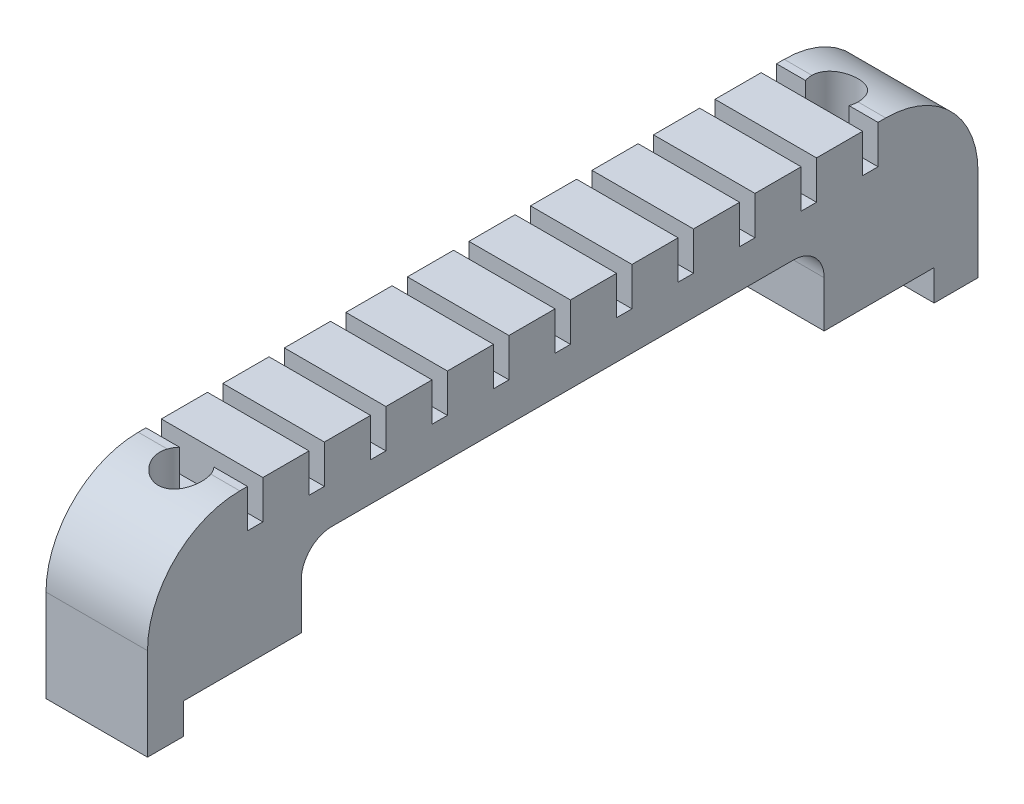
SolidWorks part; units mm, degrees
ref_plane "前视基准面" through (0, 0, 0) normal (0, 0, 1) x (1, 0, 0)
ref_plane "上视基准面" through (0, 0, 0) normal (0, 1, 0) x (1, 0, 0)
ref_plane "右视基准面" through (0, 0, 0) normal (1, 0, 0) x (0, 0, -1)
other "Configuration Table"
sketch "草图1" plane through (0, 0, 0) normal (0, 1, 0) x (1, 0, 0)
  line L0 (-40, 24) -> (40, 24) construction
  line L1 (-40, 24) -> (-40, -24) construction
  line L2 (-40, -24) -> (40, -24) construction
  line L3 (40, 24) -> (40, -24) construction
  line L4 (-40, 24) -> (40, -24) construction
  line L5 (-40, -24) -> (40, 24) construction
  line L6 (-34, 18) -> (34, 18) construction
  line L7 (-34, 18) -> (-34, -18) construction
  line L8 (-34, -18) -> (34, -18) construction
  line L9 (34, 18) -> (34, -18) construction
  line L10 (-34, 18) -> (34, -18) construction
  line L11 (-34, -18) -> (34, 18) construction
  line L13 (-28.3, 27) -> (-21.7, 27)
  line L14 (-28.3, 27) -> (-28.3, -27)
  line L15 (-28.3, -27) -> (-21.7, -27)
  line L16 (-21.7, 27) -> (-21.7, -27)
  line L17 (-28.3, 27) -> (-21.7, -27) construction
  line L18 (-28.3, -27) -> (-21.7, 27) construction
  circle A0 centre (25, -21.5) radius 1.5 construction
  circle A1 centre (25, 21) radius 1.5 construction
  circle A2 centre (0, 21) radius 1.5 construction
  circle A3 centre (0, -21.5) radius 1.5 construction
  circle A4 centre (-25, -21.5) radius 1.5
  circle A5 centre (-25, 21) radius 1.5
  point P0 (0, 0)
  point P17 (0, 0)
  point P22 (-25, 0)
  dimension "D1" = 48
  dimension "D2" = 36
  dimension "D3" = 68
  dimension "D4" = 6.6
  dimension "D5" = 25
  dimension "D6" = 54
extrude "凸台-拉伸1" add sketch "草图1" along normal blind 12
fillet "圆角1" radius 6 2 edges at (-25, 12, -27) (-25, 12, 27)
sketch "草图2" plane through (-28.3, 0, 0) normal (-1, 0, 0) x (0, 0, 1)
  line L1 (-17, 7) -> (17, 7)
  line L2 (-17, 7) -> (-17, -7)
  line L3 (-17, -7) -> (17, -7)
  line L4 (17, 7) -> (17, -7)
  line L5 (-17, 7) -> (17, -7) construction
  line L6 (-17, -7) -> (17, 7) construction
  point P0 (0, 0)
  dimension "D1" = 14
  dimension "D2" = 34
extrude "切除-拉伸1" cut sketch "草图2" against normal blind 20
fillet "圆角2" radius 2 2 edges at (-25, 7, 17) (-25, 7, -17)
sketch "草图3" plane through (-28.3, 0, 0) normal (-1, 0, 0) x (0, 0, 1)
  line L0 (-21, 12) -> (21, 12) construction
  line L1 (-0.5, 9.5) -> (0.5, 9.5)
  line L2 (-0.5, 9.5) -> (-0.5, 12)
  line L3 (-0.5, 12) -> (0.5, 12)
  line L4 (0.5, 9.5) -> (0.5, 12)
  line L5 (-0.5, 9.5) -> (0.5, 12) construction
  line L6 (-0.5, 12) -> (0.5, 9.5) construction
  line L7 (3.5, 9.5) -> (3.5, 12)
  line L8 (3.5, 12) -> (4.5, 12)
  line L9 (4.5, 9.5) -> (4.5, 12)
  line L10 (3.5, 9.5) -> (4.5, 9.5)
  line L11 (7.5, 9.5) -> (7.5, 12)
  line L12 (7.5, 12) -> (8.5, 12)
  line L13 (8.5, 9.5) -> (8.5, 12)
  line L14 (7.5, 9.5) -> (8.5, 9.5)
  line L15 (11.5, 9.5) -> (11.5, 12)
  line L16 (11.5, 12) -> (12.5, 12)
  line L17 (12.5, 9.5) -> (12.5, 12)
  line L18 (11.5, 9.5) -> (12.5, 9.5)
  line L19 (15.5, 9.5) -> (15.5, 12)
  line L20 (15.5, 12) -> (16.5, 12)
  line L21 (16.5, 9.5) -> (16.5, 12)
  line L22 (15.5, 9.5) -> (16.5, 9.5)
  line L23 (19.5, 9.5) -> (19.5, 12)
  line L24 (19.5, 12) -> (20.5, 12)
  line L25 (20.5, 9.5) -> (20.5, 12)
  line L26 (19.5, 9.5) -> (20.5, 9.5)
  line L27 (-4.5, 9.5) -> (-3.5, 9.5)
  line L28 (-4.5, 9.5) -> (-4.5, 12)
  line L29 (-4.5, 12) -> (-3.5, 12)
  line L30 (-3.5, 9.5) -> (-3.5, 12)
  line L31 (-4.5, 9.5) -> (-3.5, 12) construction
  line L32 (-4.5, 12) -> (-3.5, 9.5) construction
  line L33 (-8.5, 9.5) -> (-7.5, 9.5)
  line L34 (-8.5, 9.5) -> (-8.5, 12)
  line L35 (-8.5, 12) -> (-7.5, 12)
  line L36 (-7.5, 9.5) -> (-7.5, 12)
  line L37 (-8.5, 9.5) -> (-7.5, 12) construction
  line L38 (-8.5, 12) -> (-7.5, 9.5) construction
  line L39 (-12.5, 9.5) -> (-11.5, 9.5)
  line L40 (-12.5, 9.5) -> (-12.5, 12)
  line L41 (-12.5, 12) -> (-11.5, 12)
  line L42 (-11.5, 9.5) -> (-11.5, 12)
  line L43 (-12.5, 9.5) -> (-11.5, 12) construction
  line L44 (-12.5, 12) -> (-11.5, 9.5) construction
  line L45 (-16.5, 9.5) -> (-15.5, 9.5)
  line L46 (-16.5, 9.5) -> (-16.5, 12)
  line L47 (-16.5, 12) -> (-15.5, 12)
  line L48 (-15.5, 9.5) -> (-15.5, 12)
  line L49 (-16.5, 9.5) -> (-15.5, 12) construction
  line L50 (-16.5, 12) -> (-15.5, 9.5) construction
  line L51 (-20.5, 9.5) -> (-19.5, 9.5)
  line L52 (-20.5, 9.5) -> (-20.5, 12)
  line L53 (-20.5, 12) -> (-19.5, 12)
  line L54 (-19.5, 9.5) -> (-19.5, 12)
  line L55 (-20.5, 9.5) -> (-19.5, 12) construction
  line L56 (-20.5, 12) -> (-19.5, 9.5) construction
  point P0 (0, 10.75)
  point P30 (-4, 10.75)
  point P35 (-8, 10.75)
  point P40 (-12, 10.75)
  point P45 (-16, 10.75)
  point P50 (-20, 10.75)
  dimension "D1" = 1
  dimension "D2" = 2.5
extrude "切除-拉伸2" cut sketch "草图3" against normal through all
sketch "草图4" plane through (0, 0, 0) normal (0, -1, 0) x (1, 0, 0)
  line L0 (-25, 21.5) -> (-25, -21) construction
  line L2 (-32.2789, 24.65) -> (-17.7211, 24.65)
  line L3 (-32.2789, 24.65) -> (-32.2789, -24.15)
  line L4 (-32.2789, -24.15) -> (-17.7211, -24.15)
  line L5 (-17.7211, 24.65) -> (-17.7211, -24.15)
  line L6 (-32.2789, 24.65) -> (-17.7211, -24.15) construction
  line L7 (-32.2789, -24.15) -> (-17.7211, 24.65) construction
  point P4 (-25, 0.25)
  dimension "D1" = 48.8
extrude "切除-拉伸3" cut sketch "草图4" against normal blind 2
sketch "草图6" plane through (0, 2, 0) normal (0, -1, 0) x (1, 0, 0)
  circle A0 centre (-25, 21.5) radius 1.5
  circle A1 centre (-25, 21.5) radius 1
  circle A5 centre (-25, -21) radius 1
  circle A6 centre (-25, -21) radius 1.5
  dimension "D1" = 2
  dimension "D2" = 3
  dimension "D3" = 3
  dimension "D4" = 2
extrude "凸台-拉伸2" add sketch "草图6" against normal blind 4
